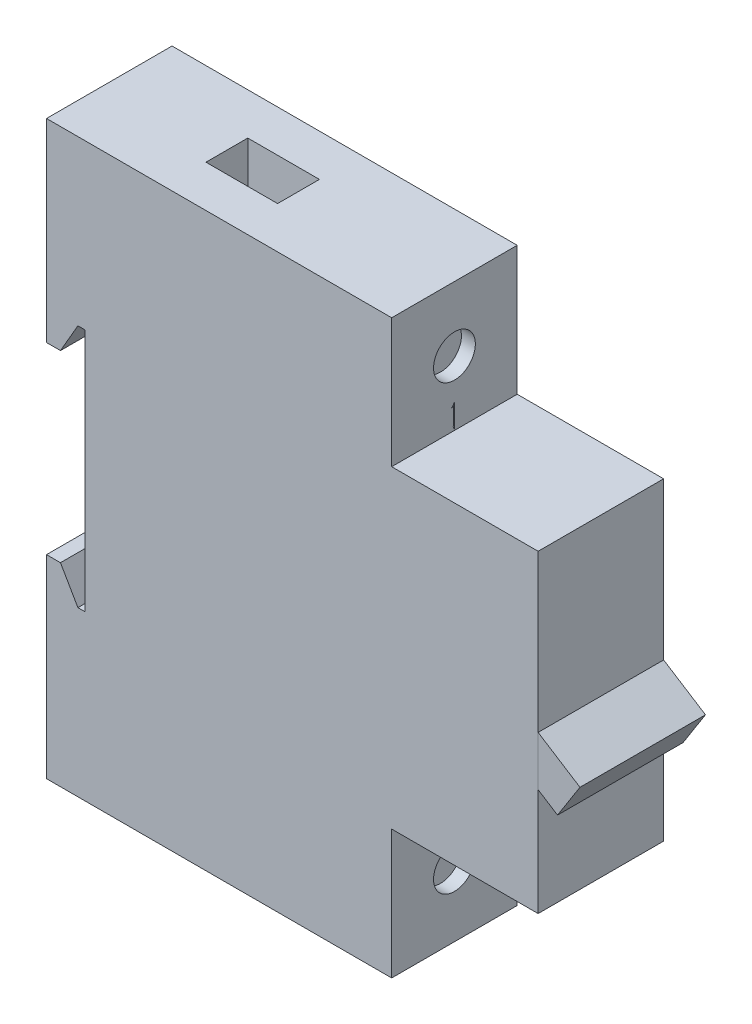
SolidWorks part; units mm, degrees
material "普通碳钢"
ref_plane "前视基准面" through (0, 0, 0) normal (0, 0, 1) x (1, 0, 0)
ref_plane "上视基准面" through (0, 0, 0) normal (0, 1, 0) x (1, 0, 0)
ref_plane "右视基准面" through (0, 0, 0) normal (1, 0, 0) x (0, 0, -1)
sketch "草图1" plane through (0, 0, 0) normal (0, 0, 1) x (1, 0, 0)
  line L0 (0, 0) -> (97.4474, 0) construction
  line L1 (0, 13.1699) -> (2, 13.1699)
  line L2 (2, 13.1699) -> (4.5, 17.5)
  line L3 (4.5, 17.5) -> (5.5, 17.5)
  line L4 (5.5, 17.5) -> (5.5, -17.5)
  line L5 (0, 13.1699) -> (0, 41)
  line L6 (0, 41) -> (49.5, 41)
  line L7 (49.5, 41) -> (49.5, 22.5)
  line L8 (49.5, 22.5) -> (70.5, 22.5)
  line L9 (70.5, 22.5) -> (70.5, -22.5)
  line L10 (49.5, -22.5) -> (70.5, -22.5)
  line L11 (49.5, -41) -> (49.5, -22.5)
  line L12 (0, -41) -> (49.5, -41)
  line L13 (0, -13.1699) -> (0, -41)
  line L14 (4.5, -17.5) -> (5.5, -17.5)
  line L15 (2, -13.1699) -> (4.5, -17.5)
  line L16 (0, -13.1699) -> (2, -13.1699)
  point P14 (70.5, 0)
  point P19 (5.5, 0)
  dimension "D1" = 35
  dimension "D2" = 45
  dimension "D3" = 82
  dimension "D4" = 5.5
  dimension "D5" = 1
  dimension "D6" = 2
  dimension "D7" = 120
  dimension "D8" = 44
  dimension "D9" = 65
extrude "凸台-拉伸1" add sketch "草图1" against normal blind 18
sketch "草图2" plane through (49.5, 0, 0) normal (1, 0, 0) x (0, 0, -1)
  line L0 (0, 22.5) -> (0, 41) construction
  line L1 (18, 41) -> (0, 41) construction
  circle A0 centre (9, 31.75) radius 3
  point P4 (0, 31.75)
  point P7 (9, 41)
  dimension "D1" = 6
extrude "切除-拉伸1" cut sketch "草图2" against normal blind 2
sketch "草图7" plane through (0, 41, 0) normal (0, 1, 0) x (1, 0, 0)
  line L0 (0, 18) -> (0, 0) construction
  line L1 (16.8628, 6) -> (27.1372, 6)
  line L2 (16.8628, 6) -> (16.8628, 12)
  line L3 (16.8628, 12) -> (27.1372, 12)
  line L4 (27.1372, 6) -> (27.1372, 12)
  line L5 (16.8628, 6) -> (27.1372, 12) construction
  line L6 (16.8628, 12) -> (27.1372, 6) construction
  point P0 (22, 9)
  point P7 (0, 9)
  dimension "D1" = 22
  dimension "D2" = 6
extrude "切除-拉伸2" cut sketch "草图7" against normal blind 8
mirror "镜向1" about plane through (0, 0, 0) normal (0, 1, 0) of "切除-拉伸2", "切除-拉伸1"
sketch "草图3" plane through (47.5, 0, 0) normal (1, 0, 0) x (0, 0, -1)
  point P0 (9, 31.75)
  point P1 (9, -31.75)
sketch "草图4" plane through (0, 0, 0) normal (0, 0, 1) x (1, 0, 0)
  line L0 (70.5, 0) -> (76.5, -3.812)
  line L1 (70.5, -22.5) -> (70.5, 22.5) construction
  line L2 (76.5, -3.812) -> (73.2825, -8.8763)
  line L3 (73.2825, -8.8763) -> (70.5, -7.1085)
  line L4 (70.5, -7.1085) -> (70.5, 0)
  line L5 (5.5, 17.5) -> (5.5, -17.5) construction
  dimension "D1" = 71
  dimension "D2" = 6
  dimension "D3" = 57.571
extrude "凸台-拉伸3" add sketch "草图4" against normal through all
sketch "草图5" plane through (0, 0, 0) normal (0, 0, 1) x (1, 0, 0)
  line L0 (70.5, 0) -> (70.5, -7.1085)
split line "分割线1"
chamfer "倒角1" [suppressed] distance 0.2 angle 45
sketch "0_0_Point" plane through (0, 33, 0) normal (0, 1, 0) x (1, 0, 0)
  point P0 (22, 9)
sketch "0_1_Point" plane through (0, -33, 0) normal (0, -1, 0) x (1, 0, 0)
  point P0 (22, -9)
sketch "草图10" plane through (49.5, 0, 0) normal (1, 0, 0) x (0, 0, -1)
  line L0 (7.5191, -26.5) -> (10.1694, -26.5) construction
  line L1 (18, -22.5) -> (0, -22.5) construction
  text T0 "1"
  text T1 "2"
  dimension "D1" = 4
extrude "切除-拉伸3" cut sketch "草图10" against normal blind 1
other "0_0" parameters "直径"=2, "端头长度"=2
ref_axis "基准轴1" through (22, 43, -9) along (0, -1, 0)
other "0_1" parameters "直径"=2, "端头长度"=2
ref_axis "基准轴2" through (22, -43, -9) along (0, 1, 0)
equation "\"D1@草图7\"=\"D8@草图1\"/2"
